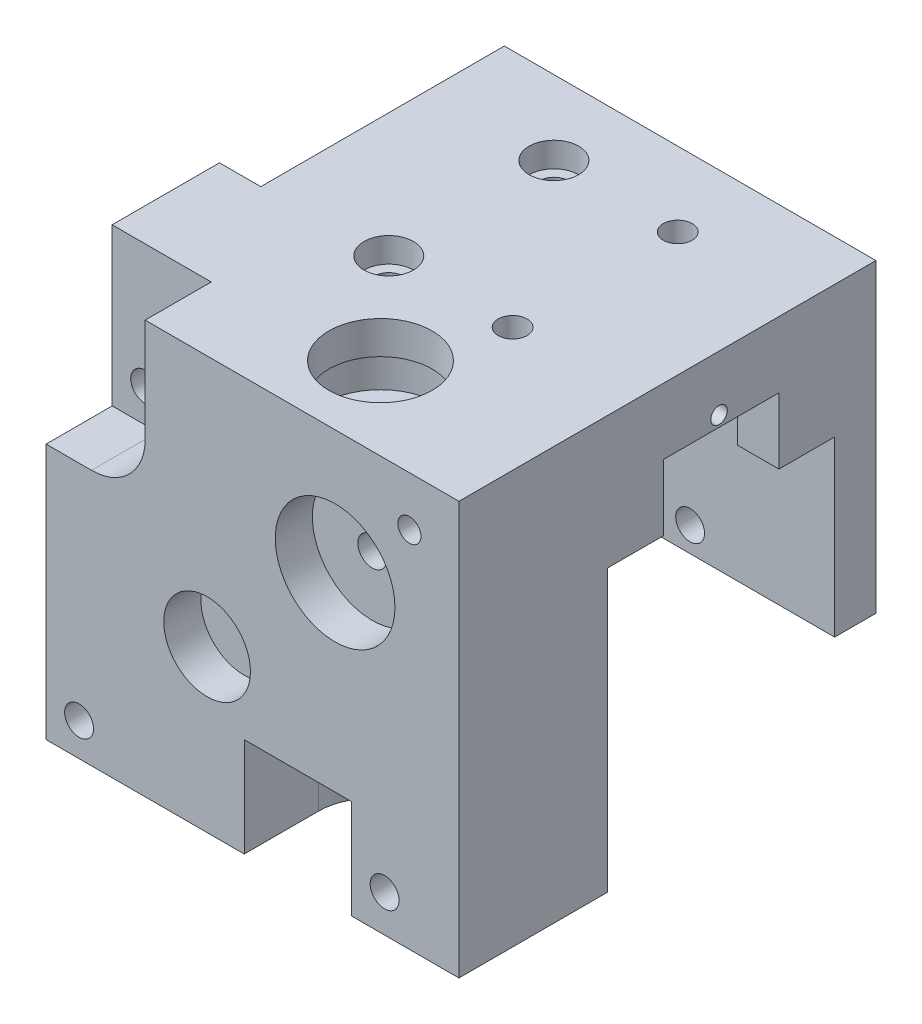
SolidWorks part; units mm, degrees
material "ABS"
ref_plane "Front Plane" through (0, 0, 0) normal (0, 0, 1) x (1, 0, 0)
ref_plane "Top Plane" through (0, 0, 0) normal (0, 1, 0) x (1, 0, 0)
ref_plane "Right Plane" through (0, 0, 0) normal (1, 0, 0) x (0, 0, -1)
sketch "Sketch1" plane through (0, 0, 0) normal (0, 1, 0) x (1, 0, 0)
  line L1 (-17.5, -14) -> (17.5, -14)
  line L2 (-17.5, -14) -> (-17.5, 14)
  line L3 (-17.5, 14) -> (17.5, 14)
  line L4 (17.5, -14) -> (17.5, 14)
  line L5 (-17.5, -14) -> (17.5, 14) construction
  line L6 (-17.5, 14) -> (17.5, -14) construction
  point P0 (0, 0)
  dimension "D1" = 28
  dimension "D2" = 35
extrude "Boss-Extrude1" add sketch "Sketch1" along normal blind 4
sketch "Sketch2" plane through (0, 4, 0) normal (0, 1, 0) x (1, 0, 0)
  line L0 (-17.5, -14) -> (17.5, -14) construction
  line L1 (-17.5, 14) -> (-17.5, -14) construction
  line L2 (-17.5, -14) -> (17.5, -14) construction
  line L3 (17.5, 14) -> (-17.5, 14) construction
  circle A0 centre (-7.5, -10) radius 1.75
  circle A1 centre (-7.5, 10) radius 1.75
  circle A2 centre (7.5, -10) radius 1.75
  circle A3 centre (7.5, 10) radius 1.75
  dimension "D1" = 3.5
  dimension "D2" = 3.5
  dimension "D5" = 3.5
  dimension "D8" = 3.5
  dimension "D3" = 20
  dimension "D4" = 4
  dimension "D6" = 15
  dimension "D7" = 10
  dimension "D9" = 15
  dimension "D10" = 4
  dimension "D11" = 4
extrude "Cut-Extrude1" cut sketch "Sketch2" against normal through all
sketch "Sketch3" plane through (0, 0, 14) normal (0, 0, 1) x (1, 0, 0)
  line L0 (17.5, 4) -> (17.5, 0) construction
  line L1 (-17.5, 4) -> (17.5, 4)
  line L2 (-17.5, 4) -> (-17.5, -46)
  line L3 (-17.5, -46) -> (17.5, -46)
  line L4 (17.5, 4) -> (17.5, -46)
  dimension "D1" = 50
extrude "Boss-Extrude2" add sketch "Sketch3" along normal blind 17.5 and the other way blind 0.5
sketch "Sketch7" plane through (0, 0, -14) normal (0, 0, -1) x (-1, 0, 0)
  line L1 (-17.5, 4) -> (17.5, 4)
  line L2 (-17.5, 4) -> (-17.5, -33)
  line L3 (-17.5, -33) -> (17.5, -33)
  line L4 (17.5, 4) -> (17.5, -33)
  line L6 (17.5, 4) -> (17.5, 0) construction
  dimension "D1" = 37
extrude "Boss-Extrude3" add sketch "Sketch7" along normal blind 5
sketch "Sketch10" plane through (0, 0, -19) normal (0, 0, -1) x (-1, 0, 0)
  line L1 (0, 4) -> (0, -33) construction
  line L3 (17.5, 4) -> (-17.5, 4) construction
  line L4 (-17.5, -33) -> (17.5, -33) construction
  circle A1 centre (-5, -30) radius 1.75
  circle A2 centre (5, -30) radius 1.75
  dimension "D1" = 3
  dimension "D2" = 3.5
  dimension "D4" = 3.5
  dimension "D3" = 5
  dimension "D5" = 5
extrude "Cut-Extrude6" cut sketch "Sketch10" against normal blind 5
sketch "Sketch18" plane through (0, 4, 0) normal (0, 1, 0) x (1, 0, 0)
  line L0 (-17.5, -10) -> (-10.5, -10)
  line L1 (-17.5, 19) -> (-17.5, -31.5) construction
  line L2 (-10.5, -10) -> (-10.5, -11.5)
  line L3 (-10.5, -11.5) -> (-17.5, -11.5)
  line L4 (-17.5, -11.5) -> (-17.5, -10)
  line L5 (17.5, 10) -> (10.5, 10)
  line L6 (17.5, -31.5) -> (17.5, 19) construction
  line L7 (10.5, 10) -> (10.5, 11.5)
  line L8 (10.5, 11.5) -> (17.5, 11.5)
  line L9 (17.5, 11.5) -> (17.5, 10)
  circle A0 centre (-7.5, -10) radius 1.75 construction
  circle A1 centre (7.5, 10) radius 1.75 construction
  dimension "D4" = 3
  dimension "D1" = 0
  dimension "D2" = 3
  dimension "D3" = 1.5
  dimension "D5" = 0
  dimension "D6" = 1.5
extrude "Cut-Extrude14" [suppressed] cut sketch "Sketch18" against normal through all
sketch "Sketch19" plane through (0, 4, 0) normal (0, 1, 0) x (1, 0, 0)
  line L0 (-17.5, 19) -> (-17.5, -31.5) construction
  line L1 (17.5, -31.5) -> (17.5, 19) construction
  circle A0 centre (-7.5, 0) radius 1.75
  circle A1 centre (7.5, 0) radius 1.75
  dimension "D3" = 3.5
  dimension "D4" = 3.5
  dimension "D1" = 10
  dimension "D2" = 10
extrude "Cut-Extrude15" [suppressed] cut sketch "Sketch19" against normal through all
sketch "Sketch20" [suppressed] plane through (0, 0, 0) normal (0, -1, 0) x (1, 0, 0)
  line L1 (10.9641, 0) -> (9.2321, 3)
  line L2 (9.2321, 3) -> (5.7679, 3)
  line L3 (5.7679, 3) -> (4.0359, 0)
  line L4 (4.0359, 0) -> (5.7679, -3)
  line L5 (5.7679, -3) -> (9.2321, -3)
  line L6 (9.2321, -3) -> (10.9641, 0)
  line L7 (-10.9641, 0) -> (-9.2321, -3)
  line L8 (-9.2321, -3) -> (-5.7679, -3)
  line L9 (-5.7679, -3) -> (-4.0359, 0)
  line L10 (-4.0359, 0) -> (-5.7679, 3)
  line L11 (-5.7679, 3) -> (-9.2321, 3)
  line L12 (-9.2321, 3) -> (-10.9641, 0)
  circle A0 centre (7.5, 0) radius 3 construction
  circle A1 centre (-7.5, 0) radius 3 construction
  dimension "D1" = 6
  dimension "D2" = 6
extrude "Cut-Extrude16" [suppressed] cut sketch "Sketch20" against normal blind 3
sketch "Sketch21" [suppressed] plane through (0, 4, 0) normal (0, 1, 0) x (1, 0, 0)
  line L0 (-10.5, -10) -> (-17.5, -10) construction
  circle A0 centre (-17, -10) radius 0.5
  dimension "D1" = 1
extrude "Cut-Extrude17" [suppressed] cut sketch "Sketch21" against normal blind 4
pattern_linear "LPattern2" [suppressed] count 4 spacing 2 of bodies 121
fillet "Fillet2" [suppressed] radius 0.15
sketch "Sketch24" plane through (-17.5, 0, 0) normal (-1, 0, 0) x (0, 0, 1)
  line L5 (31.5, -46) -> (13.5, -46) construction
  line L6 (13.5, -46) -> (31.5, -46)
  line L7 (13.5, -46) -> (13.5, 0)
  line L8 (13.5, 0) -> (31.5, 0)
  line L9 (31.5, -46) -> (31.5, 0)
  line L10 (13.5, 0) -> (13.5, -46) construction
  line L11 (31.5, 4) -> (31.5, -46) construction
extrude "Boss-Extrude4" add sketch "Sketch24" along normal blind 10
sketch "Sketch37" plane through (-17.5, 0, 0) normal (-1, 0, 0) x (0, 0, 1)
  line L1 (10.5, 4) -> (23.5, 4)
  line L2 (10.5, 4) -> (10.5, -10)
  line L3 (10.5, -10) -> (23.5, -10)
  line L4 (23.5, 4) -> (23.5, -10)
  dimension "D1" = 3
  dimension "D2" = 10
  dimension "D3" = 14
extrude "Boss-Extrude9" add sketch "Sketch37" along normal blind 10
sketch "Sketch22" plane through (0, 0, 31.5) normal (0, 0, 1) x (1, 0, 0)
  line L0 (-27.5, -46) -> (-27.5, 0) construction
  line L1 (-15.5, 0) -> (-27.5, 0)
  line L2 (-27.5, -46) -> (17.5, -46) construction
  line L4 (-27.5, 0) -> (-17.5, 0) construction
  line L5 (-27.5, -46) -> (17.5, -46) construction
  line L6 (-27.5, 0) -> (-27.5, -15)
  line L9 (-27.5, -15) -> (-22, -15)
  line L10 (-15.5, 0) -> (-15.5, -8.5)
  line L11 (9.5, -46) -> (-3.5, -46)
  line L12 (9.5, -46) -> (9.5, -34)
  line L13 (9.5, -34) -> (-3.5, -34)
  line L14 (-3.5, -46) -> (-3.5, -34)
  line L16 (-15.5, 0) -> (-17.5, 0)
  line L17 (-15.5, 0) -> (-15.5, 4)
  line L18 (-15.5, 4) -> (-17.5, 4)
  line L19 (-17.5, 0) -> (-17.5, 4)
  circle A0 centre (-23.5, -42) radius 1.75
  circle A1 centre (13.5, -41.5) radius 1.75
  circle A3 centre (7.5, -11) radius 7.25
  circle A4 centre (-8, -26.5) radius 5.25
  arc A5 (-22, -15) -> (-15.5, -8.5) centre (-22, -8.5) ccw
  circle A6 centre (7.5, -11) radius 1.75
  circle A7 centre (-23.5, -11) radius 1.75
  point P21 (-15.5, -15)
  line M3 (-17.5, 4) -> (-17.5, 0)
  line M6 (17.5, 4) -> (-17.5, 4)
  line M24 (-17.5, 0) -> (-27.5, 0)
  line M25 (-27.5, 0) -> (-27.5, -46)
  dimension "D3" = 3.5
  dimension "D6" = 35
  dimension "D7" = 3.5
  dimension "D9" = 14.5
  dimension "D11" = 10.5
  dimension "D15" = 6.5
  dimension "D22" = 3.5
  dimension "D23" = 3.5
  dimension "D2" = 4
  dimension "D4" = 4.5
  dimension "D5" = 4
  dimension "D8" = 12
  dimension "D10" = 35
  dimension "D12" = 19.5
  dimension "D13" = 19.5
  dimension "D14" = 31
  dimension "D16" = 24
  dimension "D17" = 13
  dimension "D18" = 12
  dimension "D19" = 41
  dimension "D20" = 4
  dimension "D21" = 35
extrude "Cut-Extrude19" cut sketch "Sketch22" against normal up to next contours A0 | A1 | A7 | A6 region at (-23.5, -42, 31.5) region at (13.5, -41.5, 31.5) region at (7.5, -11, 31.5) region at (-23.5, -11, 31.5)
extrude "Cut-Extrude20" cut sketch "Sketch22<3>" against normal blind 4.5 contours A3 | A4
sketch "Sketch22<3>" plane through (0, 0, 31.5) normal (0, 0, 1) x (1, 0, 0) same geometry as "Sketch22"
extrude "Cut-Extrude24" cut sketch "Sketch22<5>" against normal blind 8 contours L9 A5 L10 L1 A7 M24 M25 | L1 L17 M6 M3 region at (-21.6364, -6.9513, 31.5) region at (-16.5, 2, 31.5)
sketch "Sketch22<5>" plane through (0, 0, 31.5) normal (0, 0, 1) x (1, 0, 0) same geometry as "Sketch22"
extrude "Cut-Extrude21" cut sketch "Sketch22<4>" against normal blind 15.5 contours L14 L13 L12 L11
sketch "Sketch22<4>" plane through (0, 0, 31.5) normal (0, 0, 1) x (1, 0, 0) same geometry as "Sketch22"
fillet "Fillet3" radius 6.5 2 edges at (9.5, -40, 16) (-3.5, -40, 16)
sketch "Sketch26" plane through (0, -34, 0) normal (0, -1, 0) x (1, 0, 0)
  line L0 (9.5, 31.5) -> (-3.5, 31.5) construction
  line L1 (-3.5, 22.5) -> (-3.5, 31.5) construction
  circle A0 centre (3, 21.5) radius 2.25
  dimension "D1" = 4.5
  dimension "D2" = 10
  dimension "D3" = 6.5
extrude "Cut-Extrude22" cut sketch "Sketch26" against normal through all
sketch "Sketch27" plane through (0, 4, 0) normal (0, 1, 0) x (1, 0, 0)
  circle A0 centre (3, -21.5) radius 6.25
  dimension "D1" = 12.5
extrude "Cut-Extrude23" cut sketch "Sketch27" against normal blind 8
sketch "Sketch41" plane through (-27.5, 0, 0) normal (-1, 0, 0) x (0, 0, 1)
  line L0 (13.5, -10) -> (13.5, -46) construction
  line L1 (13.5, -46) -> (31.5, -46) construction
  line L2 (20.5, -42.5) -> (20.5, -39)
  line L15 (23, -42.5) -> (23, -39)
  line L16 (17, -46) -> (17, -48.5)
  line L17 (20.5, -39) -> (23, -39)
  line L18 (17, -46) -> (21.8734, -46)
  circle A0 centre (17, -42.5) radius 1.25
  arc A1 (17, -46) -> (20.5, -42.5) centre (17, -42.5) ccw
  arc A2 (17, -48.5) -> (23, -42.5) centre (17, -42.5) ccw
  line M16 (13.5, -46) -> (31.5, -46)
  dimension "D5" = 2.5
  dimension "D1" = 3.5
  dimension "D2" = 3.5
  dimension "D3" = 3.5
  dimension "D4" = 2.5
extrude "Boss-Extrude10" [suppressed] add sketch "Sketch41" along normal blind 2.5 contours A0 | A2 L15 L17 L2 A1 M16
sketch "Sketch43" plane through (17.5, 0, 0) normal (1, 0, 0) x (0, 0, -1)
  line L0 (-31.5, -46) -> (-31.5, 4)
  line L1 (-31.5, 4) -> (19, 4)
  line L2 (19, 4) -> (19, -33)
  line L3 (19, -33) -> (14, -33)
  line L6 (-13.5, 0) -> (14, 0) construction
  line L7 (-31.5, -46) -> (-13.5, -46)
  line L11 (-6.75, -4) -> (-6.75, -12)
  line L12 (-6.75, -12) -> (-13.5, -12)
  line L13 (7.25, -4) -> (7.25, -12)
  line L14 (7.25, -12) -> (14, -12)
  line L15 (-6.75, -4) -> (7.25, -4)
  line L16 (-13.5, -12) -> (-13.5, -46)
  line L17 (14, -12) -> (14, -33)
  dimension "D1" = 29
  dimension "D3" = 6.75
  dimension "D4" = 12
  dimension "D5" = 14
extrude "Boss-Extrude11" add sketch "Sketch43" along normal blind 5
sketch "Sketch44" plane through (-17.5, 0, 0) normal (-1, 0, 0) x (0, 0, 1)
  line L0 (10.5, 4) -> (-19, 4)
  line L1 (-19, 4) -> (-19, -33)
  line L2 (-19, -33) -> (-14, -33)
  line L8 (-14, -33) -> (-14, -12)
  line L9 (-14, -12) -> (-7.25, -12)
  line L10 (-7.25, -12) -> (-7.25, -4)
  line L11 (-7.25, -4) -> (6.75, -4)
  line L12 (6.75, -4) -> (6.75, -12)
  line L16 (6.75, -12) -> (13.5, -12)
  line L17 (13.5, -12) -> (13.5, -10)
  line L18 (13.5, -10) -> (10.5, -10)
  line L19 (10.5, -10) -> (10.5, 4)
extrude "Boss-Extrude12" add sketch "Sketch44" along normal blind 5
sketch "Sketch29" plane through (0, 0, 13.5) normal (0, 0, -1) x (-1, 0, 0)
  line L1 (-4.1514, -11) -> (-5.8257, -8.1)
  line L2 (-5.8257, -8.1) -> (-9.1743, -8.1)
  line L3 (-9.1743, -8.1) -> (-10.8486, -11)
  line L4 (-10.8486, -11) -> (-9.1743, -13.9)
  line L5 (-9.1743, -13.9) -> (-5.8257, -13.9)
  line L6 (-5.8257, -13.9) -> (-4.1514, -11)
  line L7 (20.1514, -11) -> (21.8257, -13.9)
  line L8 (21.8257, -13.9) -> (25.1743, -13.9)
  line L9 (25.1743, -13.9) -> (26.8486, -11)
  line L10 (26.8486, -11) -> (25.1743, -8.1)
  line L11 (25.1743, -8.1) -> (21.8257, -8.1)
  line L12 (21.8257, -8.1) -> (20.1514, -11)
  line L13 (-10.1514, -41.5) -> (-11.8257, -38.6)
  line L14 (-11.8257, -38.6) -> (-15.1743, -38.6)
  line L15 (-15.1743, -38.6) -> (-16.8486, -41.5)
  line L16 (-16.8486, -41.5) -> (-15.1743, -44.4)
  line L17 (-15.1743, -44.4) -> (-11.8257, -44.4)
  line L18 (-11.8257, -44.4) -> (-10.1514, -41.5)
  line L25 (23.5, -45.3486) -> (26.4, -43.6743)
  line L26 (26.4, -43.6743) -> (26.4, -40.3257)
  line L27 (26.4, -40.3257) -> (23.5, -38.6514)
  line L28 (23.5, -38.6514) -> (20.6, -40.3257)
  line L29 (20.6, -40.3257) -> (20.6, -43.6743)
  line L30 (20.6, -43.6743) -> (23.5, -45.3486)
  circle A0 centre (-7.5, -11) radius 2.9 construction
  circle A1 centre (23.5, -11) radius 2.9 construction
  circle A2 centre (-13.5, -41.5) radius 2.9 construction
  circle A3 centre (23.5, -42) radius 2.9 construction
  dimension "D1" = 5.8
  dimension "D2" = 5.8
  dimension "D3" = 5.8
  dimension "D4" = 5.8
extrude "Cut-Extrude25" cut sketch "Sketch29" against normal blind 3 and the other way up to surface (6.75 mm away) other way up to face at (-20, -8, 6.75)
sketch "Sketch30" plane through (0, 4, 0) normal (0, 1, 0) x (1, 0, 0)
  circle A0 centre (-7.5, 10) radius 3
  circle A1 centre (-7.5, -10) radius 3
  dimension "D1" = 6
  dimension "D2" = 6
extrude "Cut-Extrude26" cut sketch "Sketch30" against normal blind 3
ref_plane "Plane1" [suppressed] through (0, 0, 0) normal (-1, 0, 0) x (0, 0, 1)
sketch "Sketch38" plane through (0, -4, 0) normal (0, 1, 0) x (1, 0, 0)
  circle A0 centre (3, -21.5) radius 7
  dimension "D1" = 14
extrude "Cut-Extrude31" cut sketch "Sketch38" along normal blind 4
sketch "Sketch39" plane through (-27.5, 0, 0) normal (-1, 0, 0) x (0, 0, 1)
  line L0 (13.5, -46) -> (17, -46)
  line L1 (13.5, -46) -> (31.5, -46) construction
  line L2 (13.5, -46) -> (13.5, -19)
  line L3 (13.5, -10) -> (13.5, -46) construction
  line L4 (13.5, -19) -> (17, -19)
  line L5 (20.5, -22.5) -> (20.5, -26)
  line L6 (20.5, -26) -> (27.5, -26)
  line L7 (27.5, -26) -> (27.5, -39)
  line L8 (27.5, -39) -> (20.5, -39)
  line L9 (20.5, -39) -> (20.5, -42.5)
  line L11 (27.5, -29) -> (23.5, -29)
  line L12 (27.5, -29) -> (27.5, -36)
  line L13 (27.5, -36) -> (23.5, -36)
  line L14 (23.5, -29) -> (23.5, -36)
  line L15 (13.5, -26) -> (18.5, -26)
  line L16 (13.5, -26) -> (13.5, -39)
  line L17 (13.5, -39) -> (18.5, -39)
  line L18 (18.5, -26) -> (18.5, -39)
  arc A0 (17, -46) -> (20.5, -42.5) centre (17, -42.5) ccw
  arc A1 (17, -19) -> (20.5, -22.5) centre (17, -22.5) cw
  point P15 (20.5, -46)
  point P18 (20.5, -19)
  dimension "D7" = 3.5
  dimension "D1" = 7
  dimension "D2" = 27
  dimension "D3" = 7
  dimension "D4" = 7
  dimension "D5" = 7
  dimension "D6" = 13
  dimension "D8" = 4
  dimension "D9" = 7
  dimension "D10" = 3
  dimension "D11" = 5
extrude "Cut-Extrude32" cut sketch "Sketch39" against normal blind 3 contours L18 L15 L2 L17 | L11 L14 L13 L7 region at (-27.5, -32.5, 16) region at (-27.5, -32.5, 25.5)
sketch "Sketch40" plane through (-27.5, 0, 0) normal (-1, 0, 0) x (0, 0, 1)
  line L0 (13.5, -10) -> (13.5, -26) construction
  line L1 (13.5, -46) -> (31.5, -46) construction
  circle A0 centre (17, -22.5) radius 1.4
  dimension "D3" = 2.8
  dimension "D1" = 3.5
  dimension "D2" = 23.5
extrude "Cut-Extrude33" cut sketch "Sketch40" against normal blind 15
sketch "Sketch42" plane through (0, 0, 31.5) normal (0, 0, 1) x (1, 0, 0)
  circle A0 centre (16.5, -2) radius 1.4
  circle A1 centre (-23.5, -42) radius 1.75 construction
  dimension "D3" = 2.8
  dimension "D1" = 40
  dimension "D2" = 40
extrude "Cut-Extrude34" cut sketch "Sketch42" against normal blind 10
sketch "Sketch45" plane through (22.5, 0, 0) normal (1, 0, 0) x (0, 0, -1)
  line L0 (-13.5, 0) -> (14, 0) construction
  circle A0 centre (0, -2.7) radius 1
  dimension "D2" = 2
  dimension "D1" = 2.7
extrude "Cut-Extrude35" cut sketch "Sketch45" against normal through all
sketch "Sketch46" plane through (-27.5, 0, 0) normal (-1, 0, 0) x (0, 0, 1)
  line L0 (13.5, -39) -> (13.5, -46) construction
  line L1 (13.5, -46) -> (31.5, -46) construction
  circle A0 centre (17, -42.5) radius 1.5
  dimension "D3" = 3
  dimension "D1" = 3.5
  dimension "D2" = 3.5
extrude "Boss-Extrude13" add sketch "Sketch46" along normal blind 2.5
sketch "Sketch47" plane through (0, 4, 0) normal (0, 1, 0) x (1, 0, 0)
  line L0 (-22.5, -10.5) -> (-22.5, 19) construction
  line L1 (-2.5, 5.4692) -> (-22.5, 5.4692)
  line L2 (-2.5, 5.4692) -> (-2.5, -4.5308)
  line L3 (-2.5, -4.5308) -> (-22.5, -4.5308)
  line L4 (-22.5, 5.4692) -> (-22.5, -4.5308)
  line L5 (-2.5, 5.4692) -> (-22.5, -4.5308) construction
  line L6 (-2.5, -4.5308) -> (-22.5, 5.4692) construction
  point P0 (-12.5, 0.4692)
  dimension "D1" = 20
  dimension "D2" = 10
